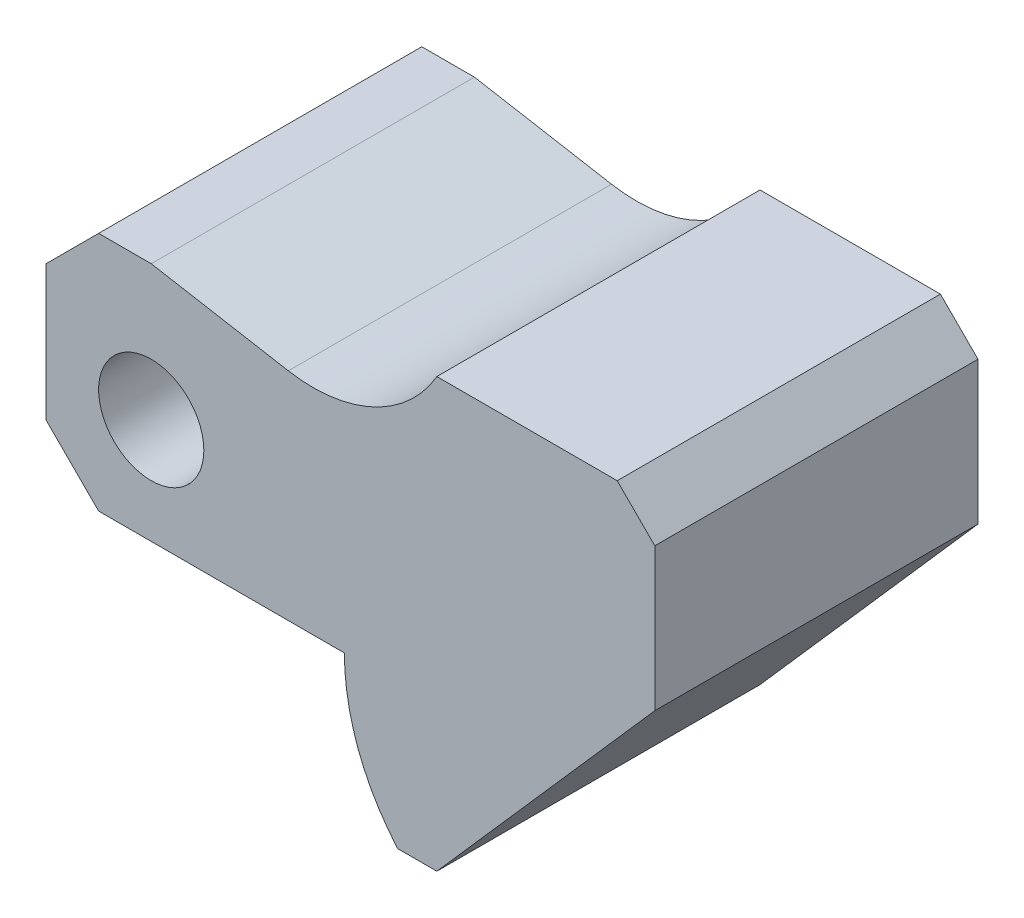
SolidWorks part; units mm, degrees
note: '?' marks a value the reader was unsure of.
material "AISI 1020"
ref_plane "VERT" through (0, 0, 0) normal (0, 0, 1) x (1, 0, 0)
ref_plane "HOR" through (0, 0, 0) normal (0, 1, 0) x (1, 0, 0)
ref_plane "CTR" through (0, 0, 0) normal (1, 0, 0) x (0, 0, -1)
ref_axis "A_X" through (56.05, 0, 0) along (-1, 0, 0)?
ref_axis "A_Y" through (0, 51.6458, 0) along (0, -1, 0)?
ref_axis "A_Z" through (0, 0, 45.15) along (0, 0, -1)?
sketch3d "PNT_CG"
  point P0 (0, 0, 0)
sketch "Sketch1" plane through (0, 0, 0) normal (1, 0, 0) x (0, 0, -1)
  line L1 (0, 0) -> (-43, 0)
  line L2 (0, 0) -> (0, 32)
  line L3 (0, 32) -> (-43, 32)
  line L4 (-43, 0) -> (-43, 32)
  dimension "D1" = 32
  dimension "D2" = 43
extrude "Boss-Extrude1" add sketch "Sketch1" against normal blind 29 contours L2 L1 L4 L3
sketch "Sketch2" plane through (0, 0, 0) normal (1, 0, 0) x (0, 0, -1)
  line L1 (0, 0) -> (-43, 0)
  line L2 (0, 0) -> (0, -19)
  line L3 (0, -19) -> (-43, -19)
  line L4 (-43, 0) -> (-43, -19)
  line L5 (0, 0) -> (-43, 0)
  line L6 (0, 0) -> (0, 38)
  line L7 (0, 38) -> (-43, 38)
  line L8 (-43, 0) -> (-43, 38)
  dimension "D2" = 43
  dimension "D1" = 19
  dimension "D3" = 38
extrude "Boss-Extrude2" add sketch "Sketch2" along normal blind 52 contours L8 L1 L6 L7 | L1 L4 L3 L2
chamfer "Chamfer1" distance 7 angle 45 2 edges at (-29, 0, 21.5) (-29, 32, 21.5)
sketch "Sketch3" plane through (0, 0, 43) normal (0, 0, 1) x (1, 0, 0)
  line L0 (55, 0) -> (-55, 0) construction
  line L1 (-29, 7) -> (-29, 25) construction
  circle A0 centre (-15, 14) radius 7
  dimension "D1" = 14
  dimension "D2" = 14
  dimension "D3" = 14
extrude "Cut-Extrude1" cut sketch "Sketch3" against normal through all contours A0
chamfer "Chamfer2" distance 5 angle 45 1 edges at (52, 38, 21.5)
sketch "Sketch5" plane through (0, 0, 0) normal (0, 0, 1) x (1, 0, 0)
  line L0 (-15, 7) -> (-15, 36.7424) construction
  line L1 (-22, 14) -> (10.7918, 14) construction
  line L2 (-15, 32) -> (3.2431, 28.7833)
  line L4 (-22, 32) -> (0, 32) construction
  line L6 (23, 45.9629) -> (23, 28.4434) construction
  line L7 (0, -55) -> (0, 55) construction
  line L8 (47, 38) -> (0, 38) construction
  line L9 (52, -19) -> (52, 33) construction
  circle A0 centre (-15, 14) radius 7 construction
  arc A6 (3.2431, 28.7833) -> (23, 38) centre (6.5424, 47.4946) ccw
  point P20 (23, 38)
  point P21 (0, 29.2817)
  point P24 (0, 48.2817)
  dimension "D4" = 19
  dimension "D2" = 38
  dimension "D1" = 10
  dimension "D3" = 29
split "Split1" trim tools "Sketch5" bodies to split 103 resulting bodies 109
sketch "Sketch6" plane through (0, 0, 43) normal (0, 0, 1) x (1, 0, 0)
  line L0 (52, -19) -> (52, 14)
  line L1 (52, -19) -> (52, 33) construction
  line L2 (52, 14) -> (23, -19)
  line L3 (52, -19) -> (0, -19) construction
  line L4 (23, -19) -> (52, -19)
  dimension "D1" = 33
  dimension "D2" = 29
extrude "Cut-Extrude2" cut sketch "Sketch6" against normal blind 52
sketch "Sketch7" plane through (0, 0, 43) normal (0, 0, 1) x (1, 0, 0)
  line L0 (52, 14) -> (23, -19) construction
  line L1 (10.697, 0) -> (0, 0)
  line L5 (52, 14) -> (52, 33) construction
  line L6 (52, 14) -> (52, 26.2609) construction
  line L8 (0, 0) -> (0, -19)
  line L23 (0, -19) -> (23, -19)
  line L24 (23, -19) -> (52, 14)
  line L25 (52, 14) -> (52, 33)
  line L26 (52, 33) -> (47, 38)
  line L27 (47, 38) -> (23, 38)
  line L28 (3.2431, 28.7833) -> (-15, 32)
  line L29 (-15, 32) -> (-22, 32)
  line L30 (-22, 32) -> (-29, 25)
  line L31 (-29, 25) -> (-29, 7)
  line L32 (-29, 7) -> (-22, 0)
  line L33 (-22, 0) -> (0, 0)
  line L34 (0, 0) -> (0, -19)
  line L35 (0, -19) -> (23, -19)
  line L36 (23, -19) -> (52, 14)
  line L37 (52, 14) -> (52, 33)
  line L38 (52, 33) -> (47, 38)
  line L39 (47, 38) -> (23, 38)
  line L40 (3.2431, 28.7833) -> (-15, 32)
  line L41 (-15, 32) -> (-22, 32)
  line L42 (-22, 32) -> (-29, 25)
  line L43 (-29, 25) -> (-29, 7)
  line L44 (-29, 7) -> (-22, 0)
  line L45 (-22, 0) -> (0, 0)
  line L46 (0, 0) -> (0, -19)
  arc A1 (10.697, 0) -> (17.7881, -19) centre (39.697, 0) ccw
  arc A3 (3.2431, 28.7833) -> (23, 38) centre (6.5424, 47.4946) ccw
  arc A4 (3.2431, 28.7833) -> (23, 38) centre (6.5424, 47.4946) ccw
  point P0 (39.697, 0)
  line M7 (0, 0) -> (0, -19)
  line M8 (0, -19) -> (23, -19)
  dimension "D2" = 10.697
  dimension "D1" = 0
extrude "Cut-Extrude7" cut sketch "Sketch7" against normal through all contours A1 L1 M7 M8
equation "\"A\"= 81"
equation "\"B\"= 57"
equation "\"C\"=43"
equation "\"D2@Sketch1\"=\"C\""
equation "\"D1@Boss-Extrude1\"=\"A\"-52"
equation "\"D2@Sketch2\"=\"C\""
equation "\"D3@Sketch2\"=\"B\"-19"
equation "\"D1@Sketch6\"=\"B\"-24"
